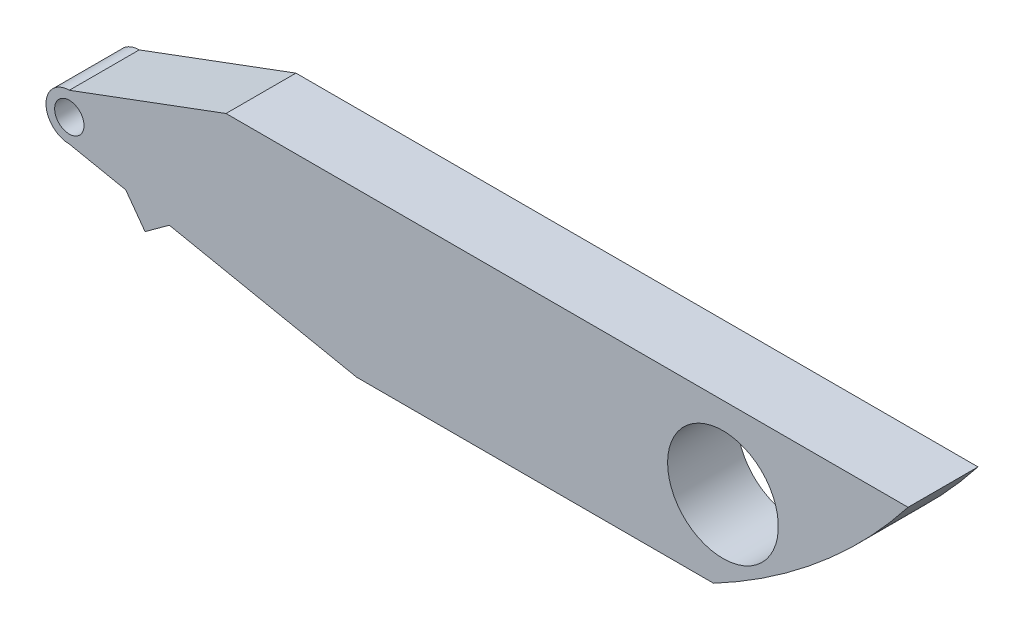
SolidWorks part; units mm, degrees
ref_plane "Front Plane" through (0, 0, 0) normal (0, 0, 1) x (1, 0, 0)
ref_plane "Top Plane" through (0, 0, 0) normal (0, 1, 0) x (1, 0, 0)
ref_plane "Right Plane" through (0, 0, 0) normal (1, 0, 0) x (0, 0, -1)
sketch "Sketch1" plane through (0, 0, 0) normal (0, 0, 1) x (1, 0, 0)
  line L1 (120.65, 22.225) -> (-120.65, 22.225)
  line L2 (120.65, 22.225) -> (120.65, -22.225)
  line L3 (120.65, -22.225) -> (-120.65, -22.225)
  line L4 (-120.65, 22.225) -> (-120.65, -22.225)
  line L5 (120.65, 22.225) -> (-120.65, -22.225) construction
  line L6 (120.65, -22.225) -> (-120.65, 22.225) construction
  point P0 (0, 0)
  dimension "D1" = 241.3
  dimension "D2" = 44.45
extrude "Boss-Extrude1" add sketch "Sketch1" along normal blind 19.06
sketch "Sketch3" plane through (0, 0, 19.06) normal (0, 0, 1) x (1, 0, 0)
  line L0 (0, 0) -> (-120.65, 0) construction
  line L1 (-120.65, 22.225) -> (-120.65, -22.225) construction
  circle A0 centre (-107.95, 0) radius 4
  dimension "D2" = 8
  dimension "D1" = 12.7
extrude "Cut-Extrude1" cut sketch "Sketch3" against normal through all
sketch "Sketch5" plane through (0, 0, 19.06) normal (0, 0, 1) x (1, 0, 0)
  line L0 (-120.65, -22.225) -> (120.65, -22.225) construction
  line L1 (-107.95, -6.35) -> (-29.6229, -22.225)
  line L2 (-107.95, 6.35) -> (-65.2393, 22.225)
  line L3 (120.65, 22.225) -> (-120.65, 22.225) construction
  line L4 (-65.2393, 22.225) -> (-120.65, 22.225)
  line L5 (-120.65, 22.225) -> (-120.65, -22.225)
  line L6 (-120.65, -22.225) -> (-29.6229, -22.225)
  line L7 (120.65, 22.225) -> (120.65, -22.225)
  line L8 (120.65, -22.225) -> (67.6371, -22.225)
  arc A0 (67.6371, -22.225) -> (120.65, 22.225) centre (-9.5799, 123.7049) ccw
  arc A2 (-107.95, 6.35) -> (-107.95, -6.35) centre (-107.95, 0) ccw
  line M3 (-120.65, 22.225) -> (-120.65, -22.225)
  line M4 (-120.65, -22.225) -> (120.65, -22.225)
  line M5 (120.65, -22.225) -> (120.65, 22.225)
  line M6 (120.65, 22.225) -> (-120.65, 22.225)
  dimension "D1" = 165.1
  dimension "D2" = 12.7
extrude "Cut-Extrude2" cut sketch "Sketch5" against normal through all contours A0 L8 M5 | A2 L2 L1 M6 M3 M4 region at (-68.9877, -15.2803, 19.06) region at (104.3043, -8.4634, 19.06)
sketch "Sketch6" plane through (0, 0, 19.06) normal (0, 0, 1) x (1, 0, 0)
  line L0 (-107.95, 0) -> (99.7595, 0) construction
  arc A0 (67.6371, -22.225) -> (120.65, 22.225) centre (-9.5799, 123.7049) ccw construction
  circle A1 centre (19.05, 0) radius 3.1347
  dimension "D1" = 127
sketch "Sketch7" plane through (0, 0, 0) normal (0, 0, -1) x (-1, 0, 0)
  line L0 (44.0204, -2.9977) -> (44.0204, 16.0523) construction
  point P3 (44.0204, -2.9977)
  point P4 (44.0204, 16.0523)
  dimension "D1" = 19.05
sketch "Sketch11" plane through (0, 0, 0) normal (0, 0, -1) x (-1, 0, 0)
  line L1 (107.95, 0) -> (-99.7595, 0) construction
  circle A1 centre (-70.2, 0) radius 15.09
  circle A2 centre (107.95, 0) radius 4 construction
  dimension "D1" = 30.18
  dimension "D2" = 178.15
extrude "Cut-Extrude3" cut sketch "Sketch11" against normal through all
sketch "Sketch12" plane through (0, 0, 0) normal (0, 0, -1) x (-1, 0, 0)
  line L3 (87.2975, -16.6927) -> (80.6869, -11.8756)
  line L4 (107.95, -6.35) -> (29.6229, -22.225) construction
  line L5 (80.6869, -11.8756) -> (92.5615, -9.4689)
  line L6 (92.5615, -9.4689) -> (87.2975, -16.6927)
  dimension "D1" = 90
  dimension "D2" = 8.1795
  dimension "D3" = 137.538
extrude "Boss-Extrude2" add sketch "Sketch12" against normal up to surface (19.06 mm away) up to face at (55.11, 0, 19.06)
sketch "Sketch13" plane through (0, 0, 0) normal (0, 0, -1) x (-1, 0, 0)
  line L0 (-91.178, 12.065) -> (-97.8581, 12.065)
  line L1 (13.9845, -12.065) -> (28.6036, -12.065)
  line L3 (2.0742, -12.065) -> (2.0742, 12.065)
  line L5 (13.9845, -12.065) -> (13.9845, 12.065)
  line L6 (2.0742, 12.065) -> (-49.222, 12.065)
  line L7 (83.0542, -1.0292) -> (86.675, -0.2954)
  line L14 (63.4122, 12.065) -> (-97.8581, 12.065)
  line L15 (-65.0721, -12.065) -> (28.6036, -12.065)
  line L16 (28.6036, -12.065) -> (83.0542, -1.0292)
  line L17 (83.0542, -1.0292) -> (85.0698, -2.498)
  line L18 (85.0698, -2.498) -> (86.675, -0.2954)
  line L19 (86.675, -0.2954) -> (93.1411, 1.0152)
  line L20 (93.1411, 1.0152) -> (63.4122, 12.065)
  line L21 (63.4122, 12.065) -> (13.9845, 12.065)
  line L22 (-49.222, -12.065) -> (2.0742, -12.065)
  line L23 (28.6036, -12.065) -> (83.0542, -1.0292)
  line L26 (86.675, -0.2954) -> (93.1411, 1.0152)
  line L27 (93.1411, 1.0152) -> (63.4122, 12.065)
  arc A0 (-91.178, 12.065) -> (-93.1394, 7.7086) centre (-70.2, 0) ccw
  arc A2 (-49.222, -12.065) -> (-49.222, 12.065) centre (-70.2, 0) ccw
  arc A4 (-97.8581, 12.065) -> (-65.0721, -12.065) centre (9.5799, 123.7049) ccw
  arc A5 (-97.8581, 12.065) -> (-93.1394, 7.7086) centre (9.5799, 123.7049) ccw
  dimension "D1" = 10.16
extrude "Cut-Extrude4" [suppressed] cut sketch "Sketch13" against normal through all
